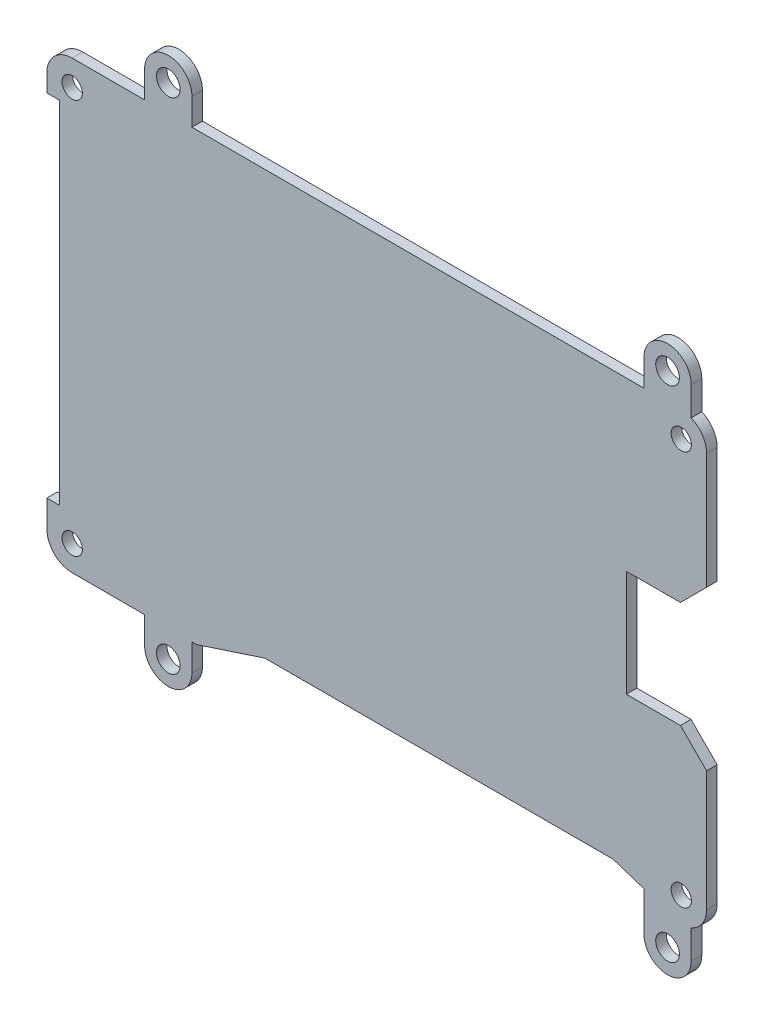
SolidWorks part; units mm, degrees
ref_plane "Front Plane" through (0, 0, 0) normal (0, 0, 1) x (1, 0, 0)
ref_plane "Top Plane" through (0, 0, 0) normal (0, 1, 0) x (1, 0, 0)
ref_plane "Right Plane" through (0, 0, 0) normal (1, 0, 0) x (0, 0, -1)
sketch "Sketch1" plane through (0, 0, 0) normal (0, 0, 1) x (1, 0, 0)
  line L5 (-301.9473, 132.8157) -> (-301.9473, 150.9704) construction
  line L6 (-305.7573, 154.7804) -> (-397.2471, 154.7804) construction
  line L7 (-401.0571, 150.9566) -> (-401.0571, 148.341) construction
  line L8 (-401.0571, 148.341) -> (-399.1521, 148.341) construction
  line L9 (-399.1521, 148.341) -> (-399.1521, 95.6449) construction
  line L10 (-399.1521, 95.6449) -> (-401.0571, 95.6449) construction
  line L11 (-401.0571, 95.6449) -> (-401.0571, 91.6593) construction
  line L12 (-397.2472, 87.8217) -> (-378.5565, 87.8217) construction
  line L13 (-378.5565, 87.8217) -> (-368.3165, 91.1883) construction
  line L14 (-368.3165, 91.1883) -> (-315.9973, 91.1883) construction
  line L15 (-315.9973, 91.1883) -> (-305.7573, 87.8217) construction
  line L16 (-301.9473, 91.6317) -> (-301.9473, 111.7465) construction
  line L17 (-301.9473, 133.5777) -> (-305.878, 129.6471)
  line L18 (-305.878, 129.6471) -> (-314.0123, 129.6471)
  line L19 (-314.0123, 129.6471) -> (-314.0123, 113.6451)
  line L20 (-314.0123, 113.6451) -> (-305.8779, 113.6451)
  line L21 (-305.8779, 113.6451) -> (-301.9473, 109.7145)
  line L22 (-301.9473, 133.5777) -> (-301.9473, 150.9704)
  line L23 (-305.7573, 154.7804) -> (-397.2471, 154.7804)
  line L24 (-401.0571, 150.9566) -> (-401.0571, 148.341)
  line L25 (-401.0571, 148.341) -> (-399.1521, 148.341)
  line L26 (-399.1521, 148.341) -> (-399.1521, 95.6449)
  line L27 (-399.1521, 95.6449) -> (-401.0571, 95.6449)
  line L28 (-401.0571, 95.6449) -> (-401.0571, 91.6593)
  line L29 (-397.2472, 87.8217) -> (-378.5565, 87.8217)
  line L30 (-378.5565, 87.8217) -> (-368.3165, 91.1883)
  line L31 (-368.3165, 91.1883) -> (-315.9973, 91.1883)
  line L32 (-315.9973, 91.1883) -> (-305.7573, 87.8217)
  line L33 (-301.9473, 91.6317) -> (-301.9473, 109.7145)
  circle A4 centre (-305.7573, 150.9704) radius 1.524
  circle A5 centre (-397.2471, 150.9704) radius 1.524
  circle A6 centre (-397.2472, 91.6317) radius 1.524
  circle A7 centre (-305.7573, 91.6317) radius 1.524
  arc A8 (-301.9473, 150.9704) -> (-305.7573, 154.7804) centre (-305.7573, 150.9704) ccw construction
  arc A9 (-397.2471, 154.7804) -> (-401.0571, 150.9566) centre (-397.2471, 150.9704) ccw construction
  arc A10 (-401.0571, 91.6593) -> (-397.2472, 87.8217) centre (-397.2472, 91.6317) ccw construction
  arc A11 (-305.7573, 87.8217) -> (-301.9473, 91.6317) centre (-305.7573, 91.6317) ccw construction
  arc A12 (-301.9473, 150.9704) -> (-305.7573, 154.7804) centre (-305.7573, 150.9704) ccw
  arc A13 (-397.2471, 154.7804) -> (-401.0571, 150.9566) centre (-397.2471, 150.9704) ccw
  arc A14 (-401.0571, 91.6593) -> (-397.2472, 87.8217) centre (-397.2472, 91.6317) ccw
  arc A15 (-305.7573, 87.8217) -> (-301.9473, 91.6317) centre (-305.7573, 91.6317) ccw
  dimension "D7" = 3.048
  dimension "D1" = 17.3927
  dimension "D2" = 3.9306
  dimension "D3" = 16.002
  dimension "D4" = 3.9307
  dimension "D5" = 8.1343
  dimension "D6" = 3.9307
extrude "Boss-Extrude1" add sketch "Sketch1" along normal blind 1.5875
sketch "Sketch2" plane through (0, 0, 1.5875) normal (0, 0, 1) x (1, 0, 0)
  line L0 (-351.5022, 121.301) -> (-351.5022, 159.401) construction
  line L1 (-301.9473, 150.9704) -> (-301.9473, 91.6317) construction
  line L2 (-401.0571, 121.301) -> (-301.9473, 121.301) construction
  line L3 (-351.5022, 83.201) -> (-351.5022, 159.401) construction
  line L4 (-361.0272, 83.201) -> (-361.0272, 159.401)
  line L5 (-341.9772, 83.201) -> (-341.9772, 159.401)
  line L6 (-361.0272, 154.7804) -> (-341.9772, 154.7804)
  line L7 (-305.7573, 154.7804) -> (-397.2471, 154.7804) construction
  line L8 (-361.0272, 91.6317) -> (-341.9772, 91.6317)
  circle A0 centre (-351.5022, 159.401) radius 3.175
  arc A1 (-361.0272, 83.201) -> (-341.9772, 83.201) centre (-351.5022, 83.201) ccw
  arc A2 (-341.9772, 159.401) -> (-361.0272, 159.401) centre (-351.5022, 159.401) ccw
  circle A3 centre (-351.5022, 83.201) radius 3.175
  point P13 (-351.5022, 121.301)
  line M11 (-305.7573, 154.7804) -> (-397.2471, 154.7804)
  line M21 (-368.3165, 91.1883) -> (-315.9973, 91.1883)
  dimension "D1" = 6.35
  dimension "D2" = 38.1
  dimension "D3" = 19.05
extrude "Boss-Extrude2" [suppressed] add sketch "Sketch2" against normal blind 1.5875 contours L5 A2 L4 A0 M11 | L4 A1 L5 A3 M21
sketch "Sketch6" plane through (0, 0, 1.5875) normal (0, 0, 1) x (1, 0, 0)
  line L0 (-386.6812, 159.8604) -> (-386.6812, 154.7804)
  line L1 (-305.7573, 154.7804) -> (-397.2471, 154.7804) construction
  line L2 (-379.8232, 159.8604) -> (-379.8232, 154.7804)
  line L3 (-379.8232, 154.7804) -> (-386.6812, 154.7804)
  line L4 (-316.3232, 159.8604) -> (-316.3232, 154.7804)
  line L5 (-316.3232, 154.7804) -> (-323.1812, 154.7804)
  line L6 (-323.1812, 154.7804) -> (-323.1812, 159.8604)
  line L7 (-383.2522, 159.8604) -> (-319.7522, 159.8604) construction
  line L8 (-351.5022, 159.8604) -> (-351.5022, 154.7804) construction
  line L10 (-351.5022, 154.7804) -> (-351.5022, 91.1883) construction
  line L11 (-368.3165, 91.1883) -> (-315.9973, 91.1883) construction
  line L12 (-361.2812, 83.5683) -> (-361.2812, 91.1883)
  line L13 (-361.2812, 91.1883) -> (-354.4232, 91.1883)
  line L14 (-354.4232, 91.1883) -> (-354.4232, 83.5683)
  circle A0 centre (-383.2522, 159.8604) radius 1.7843
  circle A1 centre (-319.7522, 159.8604) radius 1.7843
  circle A2 centre (-383.2522, 159.8604) radius 3.429
  circle A3 centre (-319.7522, 159.8604) radius 3.429
  circle A4 centre (-357.8522, 83.5683) radius 1.7145
  circle A5 centre (-357.8522, 83.5683) radius 3.429
  line M7 (-305.7573, 154.7804) -> (-397.2471, 154.7804)
  line M17 (-368.3165, 91.1883) -> (-315.9973, 91.1883)
  dimension "D2" = 6.858
  dimension "D3" = 3.5687
  dimension "D4" = 5.08
  dimension "D5" = 6.858
  dimension "D6" = 3.429
  dimension "D7" = 7.62
  dimension "D1" = 63.5
  dimension "D8" = 38.1
extrude "Boss-Extrude4" [suppressed] add sketch "Sketch6" against normal up to vertex contours A2 A0 | A2 L0 L2 M7 | A3 L6 L4 M7 | A3 A1 | A5 A4 | A5 L14 L12 M17 up to point (-368.3165, 91.1883, 0)
sketch "Sketch7" [suppressed] plane through (0, 0, 1.5875) normal (0, 0, 1) x (1, 0, 0)
  line L0 (-351.5022, 154.7804) -> (-351.5022, 91.1883) construction
  line L1 (-305.7573, 154.7804) -> (-397.2471, 154.7804) construction
  line L2 (-368.3165, 91.1883) -> (-315.9973, 91.1883) construction
  line L3 (-383.2522, 159.8604) -> (-319.7522, 159.8604) construction
  line L4 (-351.5022, 159.8604) -> (-351.5022, 154.7804) construction
  line L5 (-386.6812, 159.8604) -> (-386.6812, 154.7804)
  line L6 (-386.6812, 154.7804) -> (-379.8232, 154.7804)
  line L7 (-379.8232, 154.7804) -> (-379.8232, 159.8604)
  line L8 (-323.1812, 159.8604) -> (-323.1812, 154.7804)
  line L9 (-323.1812, 154.7804) -> (-316.3232, 154.7804)
  line L10 (-316.3232, 154.7804) -> (-316.3232, 159.8604)
  line L11 (-354.9312, 83.6604) -> (-354.9312, 91.1883)
  line L12 (-354.9312, 91.1883) -> (-348.0732, 91.1883)
  line L13 (-348.0732, 91.1883) -> (-348.0732, 83.6604)
  circle A0 centre (-383.2522, 159.8604) radius 1.7843
  circle A1 centre (-319.7522, 159.8604) radius 1.7843
  circle A2 centre (-383.2522, 159.8604) radius 3.429
  circle A3 centre (-319.7522, 159.8604) radius 3.429
  circle A4 centre (-351.5022, 83.6604) radius 1.7843
  circle A5 centre (-351.5022, 83.6604) radius 3.429
  line M5 (-305.7573, 154.7804) -> (-397.2471, 154.7804)
  line M15 (-368.3165, 91.1883) -> (-315.9973, 91.1883)
  dimension "D1" = 3.5687
  dimension "D3" = 6.858
  dimension "D2" = 63.5
  dimension "D4" = 5.08
  dimension "D5" = 76.2
extrude "Boss-Extrude5" [suppressed] add sketch "Sketch7" against normal up to vertex contours A2 L5 L7 M5 | A2 A0 | A3 L8 L10 M5 | A3 A1 | A5 A4 | A5 L13 L11 M15 up to point (-315.9973, 91.1883, 0)
sketch "Sketch8" plane through (0, 0, 1.5875) normal (0, 0, 1) x (1, 0, 0)
  line L0 (-397.2471, 154.7804) -> (-397.2472, 87.8217) construction
  line L1 (-382.8146, 158.8011) -> (-307.8146, 158.801) construction
  line L2 (-382.8146, 158.8011) -> (-382.8146, 83.8011) construction
  line L3 (-382.8146, 83.8011) -> (-307.8146, 83.801) construction
  line L4 (-307.8146, 158.801) -> (-307.8146, 83.801) construction
  line L5 (-397.2472, 121.301) -> (-382.8146, 121.301) construction
  line L6 (-386.3706, 158.8011) -> (-386.3706, 154.7804)
  line L7 (-305.7573, 154.7804) -> (-397.2471, 154.7804) construction
  line L8 (-379.2586, 158.8011) -> (-379.2586, 154.7804)
  line L9 (-311.3706, 158.801) -> (-311.3706, 154.7804)
  line L10 (-304.2586, 158.801) -> (-304.2586, 154.4733)
  line L11 (-311.3706, 83.801) -> (-311.3706, 89.6672)
  line L12 (-315.9973, 91.1883) -> (-305.7573, 87.8217) construction
  line L13 (-304.2586, 83.801) -> (-304.2586, 88.1288)
  line L14 (-379.2586, 83.8011) -> (-379.2586, 87.8217)
  line L15 (-397.2472, 87.8217) -> (-378.5565, 87.8217) construction
  line L16 (-386.3706, 83.8011) -> (-386.3706, 87.8217)
  circle A0 centre (-382.8146, 158.8011) radius 1.778
  circle A1 centre (-307.8146, 158.801) radius 1.778
  circle A2 centre (-307.8146, 83.801) radius 1.778
  circle A3 centre (-382.8146, 83.8011) radius 1.778
  circle A4 centre (-382.8146, 158.8011) radius 3.556
  circle A5 centre (-307.8146, 158.801) radius 3.556
  circle A6 centre (-307.8146, 83.801) radius 3.556
  circle A7 centre (-382.8146, 83.8011) radius 3.556
  arc A8 (-301.9473, 150.9704) -> (-305.7573, 154.7804) centre (-305.7573, 150.9704) ccw construction
  arc A9 (-305.7573, 87.8217) -> (-301.9473, 91.6317) centre (-305.7573, 91.6317) ccw construction
  arc M4 (-301.9473, 150.9704) -> (-305.7573, 154.7804) centre (-305.7573, 150.9704) ccw
  line M5 (-305.7573, 154.7804) -> (-397.2471, 154.7804)
  line M13 (-397.2472, 87.8217) -> (-378.5565, 87.8217)
  line M16 (-315.9973, 91.1883) -> (-305.7573, 87.8217)
  arc M17 (-305.7573, 87.8217) -> (-301.9473, 91.6317) centre (-305.7573, 91.6317) ccw
  dimension "D3" = 3.556
  dimension "D1" = 75
  dimension "D2" = 75
  dimension "D4" = 14.4325
  dimension "D5" = 1.778
extrude "Boss-Extrude6" add sketch "Sketch8" against normal up to vertex (1.5875 mm away) contours A4 L6 L8 M5 | A4 A0 | A5 L9 L10 M5 M4 | A5 A1 | A6 L13 L11 M17 M16 | A6 A2 | A7 L14 L16 M13 | A7 A3 region at (-382.8146, 155.1634, 1.5875) region at (-311.2874, 156.7907, 1.5875) region at (-382.8146, 162.2565, 1.5875) region at (-307.8146, 162.2565, 1.5875) region at (-308.4011, 87.5088, 1.5875) region at (-307.8146, 87.2565, 1.5875) region at (-382.8146, 87.4387, 1.5875) region at (-382.8146, 80.3456, 1.5875) up to point (-378.5565, 87.8217, 0)
